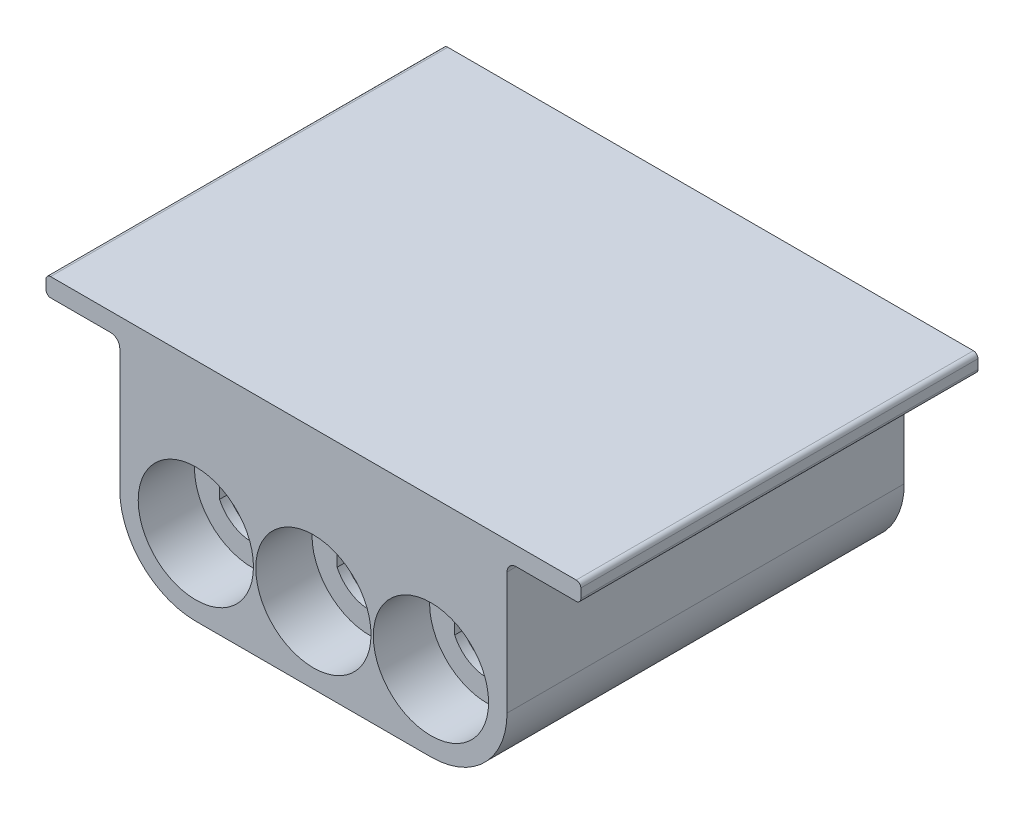
SolidWorks part; units mm, degrees
ref_plane "Front Plane" through (0, 0, 0) normal (0, 0, 1) x (1, 0, 0)
ref_plane "Top Plane" through (0, 0, 0) normal (0, 1, 0) x (1, 0, 0)
ref_plane "Right Plane" through (0, 0, 0) normal (1, 0, 0) x (0, 0, -1)
sketch "Sketch1" plane through (0, 0, 0) normal (0, 0, 1) x (1, 0, 0)
  line L0 (-163.5801, 21.2957) -> (-163.5801, 37.2957)
  line L5 (-147.0801, 53.7957) -> (-96.0801, 53.7957)
  line L6 (-79.5801, 21.2957) -> (-79.5801, 37.2957)
  line L7 (-147.0801, 4.7957) -> (-96.0801, 4.7957)
  circle A0 centre (-147.0801, 21.2957) radius 12.5
  circle A1 centre (-121.5801, 21.2957) radius 12.5
  circle A2 centre (-96.0801, 21.2957) radius 12.5
  arc A5 (-163.5801, 37.2957) -> (-147.0801, 53.7957) centre (-147.0801, 37.2957) cw
  arc A6 (-96.0801, 53.7957) -> (-79.5801, 37.2957) centre (-96.0801, 37.2957) cw
  arc A7 (-163.5801, 21.2957) -> (-147.0801, 4.7957) centre (-147.0801, 21.2957) ccw
  arc A8 (-96.0801, 4.7957) -> (-79.5801, 21.2957) centre (-96.0801, 21.2957) ccw
  circle A10 centre (-147.0801, 21.2957) radius 16.5 construction
  circle A11 centre (-96.0801, 21.2957) radius 16.5 construction
  point P9 (-96.0801, 8.7957)
  point P18 (-159.5801, 49.7957)
  point P20 (-147.0801, 8.7957)
  point P30 (-79.5801, 21.2957)
  point P35 (-130.5801, 21.2957)
  dimension "D1" = 25
  dimension "D2" = 25
  dimension "D3" = 25
  dimension "D6" = 84
  dimension "D4" = 16.5
  dimension "D5" = 4
  dimension "D7" = 49
extrude "Boss-Extrude1" add sketch "Sketch1" along normal blind 1.2
sketch "Sketch2" plane through (0, 0, 0) normal (0, 0, -1) x (-1, 0, 0)
  circle A0 centre (96.0801, 21.2957) radius 12.5 construction
  circle A1 centre (121.5801, 21.2957) radius 12.5 construction
  circle A2 centre (147.0801, 21.2957) radius 12.5 construction
  circle A3 centre (96.0801, 21.2957) radius 12.5
  circle A4 centre (121.5801, 21.2957) radius 12.5
  circle A5 centre (147.0801, 21.2957) radius 12.5
  arc A6 (135.2186, 15.1697) -> (135.2186, 27.4216) centre (147.0801, 21.2957) ccw
  arc A7 (109.7186, 15.1697) -> (133.4416, 15.1697) centre (121.5801, 21.2957) ccw
  arc A8 (107.9416, 27.4216) -> (107.9416, 15.1697) centre (96.0801, 21.2957) ccw
  arc A9 (133.4416, 27.4216) -> (109.7186, 27.4216) centre (121.5801, 21.2957) ccw
  circle A10 centre (121.5801, 21.2957) radius 13.35 construction
  circle A11 centre (96.0801, 21.2957) radius 13.35 construction
  arc A12 (107.9416, 27.4216) -> (109.7186, 27.4216) centre (108.8301, 27.8805) ccw
  circle A13 centre (147.0801, 21.2957) radius 13.35 construction
  arc A14 (109.7186, 15.1697) -> (107.9416, 15.1697) centre (108.8301, 14.7108) ccw
  arc A15 (133.4416, 27.4216) -> (135.2186, 27.4216) centre (134.3301, 27.8805) ccw
  arc A16 (133.4416, 15.1697) -> (135.2186, 15.1697) centre (134.3301, 14.7108) cw
  point P12 (109.4301, 21.2957)
  point P15 (134.9301, 21.2957)
  point P21 (160.4301, 21.2957)
  dimension "D2" = 1
  dimension "D1" = 0.85
extrude "Boss-Extrude2" add sketch "Sketch2" along normal blind 11
sketch "Sketch3" plane through (0, 0, -11) normal (0, 0, -1) x (-1, 0, 0)
  line L0 (89.3301, 18.1429) -> (89.3301, 24.4484)
  line L1 (89.3301, 18.1429) -> (89.3301, 24.4484)
  line L2 (102.8301, 18.1429) -> (102.8301, 24.4484)
  line L3 (102.8301, 18.1429) -> (102.8301, 24.4484)
  line L4 (128.3301, 18.1429) -> (128.3301, 24.4484)
  line L5 (128.3301, 18.1429) -> (128.3301, 24.4484)
  line L6 (114.8301, 18.1429) -> (114.8301, 24.4484)
  line L7 (114.8301, 18.1429) -> (114.8301, 24.4484)
  line L8 (140.3301, 24.4484) -> (140.3301, 18.1429)
  line L9 (140.3301, 24.4484) -> (140.3301, 18.1429)
  line L10 (153.8301, 24.4484) -> (153.8301, 18.1429)
  line L11 (153.8301, 24.4484) -> (153.8301, 18.1429)
  line L12 (128.6301, 18.077) -> (128.6301, 24.5144)
  line L13 (114.5301, 18.077) -> (114.5301, 24.5144)
  line L14 (103.1301, 18.077) -> (103.1301, 24.5144)
  line L15 (89.0301, 18.077) -> (89.0301, 24.5144)
  line L16 (154.1301, 24.5144) -> (154.1301, 18.077)
  line L17 (140.0301, 24.5144) -> (140.0301, 18.077)
  arc A0 (107.9416, 27.4216) -> (107.9416, 15.1697) centre (96.0801, 21.2957) ccw construction
  arc A1 (109.7186, 15.1697) -> (107.9416, 15.1697) centre (108.8301, 14.7108) ccw construction
  arc A2 (107.9416, 27.4216) -> (109.7186, 27.4216) centre (108.8301, 27.8805) ccw construction
  arc A3 (109.7186, 15.1697) -> (133.4416, 15.1697) centre (121.5801, 21.2957) ccw construction
  arc A4 (133.4416, 27.4216) -> (109.7186, 27.4216) centre (121.5801, 21.2957) ccw construction
  arc A5 (133.4416, 27.4216) -> (135.2186, 27.4216) centre (134.3301, 27.8805) ccw construction
  arc A6 (135.2186, 15.1697) -> (133.4416, 15.1697) centre (134.3301, 14.7108) ccw construction
  arc A7 (135.2186, 15.1697) -> (135.2186, 27.4216) centre (147.0801, 21.2957) ccw construction
  arc A8 (107.9416, 27.4216) -> (107.9416, 15.1697) centre (96.0801, 21.2957) ccw
  arc A9 (109.7186, 15.1697) -> (107.9416, 15.1697) centre (108.8301, 14.7108) ccw
  arc A10 (107.9416, 27.4216) -> (109.7186, 27.4216) centre (108.8301, 27.8805) ccw
  arc A11 (109.7186, 15.1697) -> (133.4416, 15.1697) centre (121.5801, 21.2957) ccw
  arc A12 (133.4416, 27.4216) -> (109.7186, 27.4216) centre (121.5801, 21.2957) ccw
  arc A13 (133.4416, 27.4216) -> (135.2186, 27.4216) centre (134.3301, 27.8805) ccw
  arc A14 (135.2186, 15.1697) -> (133.4416, 15.1697) centre (134.3301, 14.7108) ccw
  arc A15 (135.2186, 15.1697) -> (135.2186, 27.4216) centre (147.0801, 21.2957) ccw
  arc A16 (89.3301, 18.1429) -> (102.8301, 18.1429) centre (96.0801, 21.2957) ccw
  arc A17 (89.3301, 18.1429) -> (102.8301, 18.1429) centre (96.0801, 21.2957) ccw
  arc A18 (102.8301, 24.4484) -> (89.3301, 24.4484) centre (96.0801, 21.2957) ccw
  arc A19 (102.8301, 24.4484) -> (89.3301, 24.4484) centre (96.0801, 21.2957) ccw
  arc A20 (114.8301, 18.1429) -> (128.3301, 18.1429) centre (121.5801, 21.2957) ccw
  arc A21 (114.8301, 18.1429) -> (128.3301, 18.1429) centre (121.5801, 21.2957) ccw
  arc A22 (128.3301, 24.4484) -> (114.8301, 24.4484) centre (121.5801, 21.2957) ccw
  arc A23 (128.3301, 24.4484) -> (114.8301, 24.4484) centre (121.5801, 21.2957) ccw
  arc A24 (140.3301, 18.1429) -> (153.8301, 18.1429) centre (147.0801, 21.2957) ccw
  arc A25 (140.3301, 18.1429) -> (153.8301, 18.1429) centre (147.0801, 21.2957) ccw
  arc A26 (153.8301, 24.4484) -> (140.3301, 24.4484) centre (147.0801, 21.2957) ccw
  arc A27 (153.8301, 24.4484) -> (140.3301, 24.4484) centre (147.0801, 21.2957) ccw
  arc A28 (114.5301, 18.077) -> (128.6301, 18.077) centre (121.5801, 21.2957) ccw
  arc A29 (128.6301, 24.5144) -> (114.5301, 24.5144) centre (121.5801, 21.2957) ccw
  arc A30 (89.0301, 18.077) -> (103.1301, 18.077) centre (96.0801, 21.2957) ccw
  arc A31 (103.1301, 24.5144) -> (89.0301, 24.5144) centre (96.0801, 21.2957) ccw
  arc A32 (140.0301, 18.077) -> (154.1301, 18.077) centre (147.0801, 21.2957) ccw
  arc A33 (154.1301, 24.5144) -> (140.0301, 24.5144) centre (147.0801, 21.2957) ccw
  dimension "D1" = 0.3
extrude "Boss-Extrude3" add sketch "Sketch3" along normal blind 2 contours A33 L16 A32 L17 | A29 L12 A28 L13 | A31 L14 A30 L15 region at (-108.8301, 26.0589, -11)
sketch "Sketch4" plane through (0, 0, -13) normal (0, 0, -1) x (-1, 0, 0)
  line L0 (96.0801, 31.688) -> (87.0801, 26.4918) construction
  line L1 (87.0801, 26.4918) -> (87.0801, 16.0995) construction
  line L2 (87.0801, 16.0995) -> (96.0801, 10.9034) construction
  line L3 (96.0801, 10.9034) -> (105.0801, 16.0995) construction
  line L4 (105.0801, 16.0995) -> (105.0801, 26.4918) construction
  line L5 (105.0801, 26.4918) -> (96.0801, 31.688) construction
  line L6 (130.5801, 26.4918) -> (121.5801, 31.688) construction
  line L7 (121.5801, 31.688) -> (112.5801, 26.4918) construction
  line L8 (112.5801, 26.4918) -> (112.5801, 16.0995) construction
  line L9 (112.5801, 16.0995) -> (121.5801, 10.9034) construction
  line L10 (121.5801, 10.9034) -> (130.5801, 16.0995) construction
  line L11 (130.5801, 16.0995) -> (130.5801, 26.4918) construction
  line L12 (156.0801, 26.4918) -> (147.0801, 31.688) construction
  line L13 (147.0801, 31.688) -> (138.0801, 26.4918) construction
  line L14 (138.0801, 26.4918) -> (138.0801, 16.0995) construction
  line L15 (138.0801, 16.0995) -> (147.0801, 10.9034) construction
  line L16 (147.0801, 10.9034) -> (156.0801, 16.0995) construction
  line L17 (156.0801, 16.0995) -> (156.0801, 26.4918) construction
  line L18 (96.0801, 31.688) -> (87.0801, 26.4918)
  line L19 (87.0801, 26.4918) -> (87.0801, 16.0995)
  line L20 (87.0801, 16.0995) -> (96.0801, 10.9034)
  line L21 (96.0801, 10.9034) -> (105.0801, 16.0995)
  line L22 (105.0801, 16.0995) -> (105.0801, 26.4918)
  line L23 (105.0801, 26.4918) -> (96.0801, 31.688)
  line L24 (130.5801, 26.4918) -> (121.5801, 31.688)
  line L25 (121.5801, 31.688) -> (112.5801, 26.4918)
  line L26 (112.5801, 26.4918) -> (112.5801, 16.0995)
  line L27 (112.5801, 16.0995) -> (121.5801, 10.9034)
  line L28 (121.5801, 10.9034) -> (130.5801, 16.0995)
  line L29 (130.5801, 16.0995) -> (130.5801, 26.4918)
  line L30 (156.0801, 26.4918) -> (147.0801, 31.688)
  line L31 (147.0801, 31.688) -> (138.0801, 26.4918)
  line L32 (138.0801, 26.4918) -> (138.0801, 16.0995)
  line L33 (138.0801, 16.0995) -> (147.0801, 10.9034)
  line L34 (147.0801, 10.9034) -> (156.0801, 16.0995)
  line L35 (156.0801, 16.0995) -> (156.0801, 26.4918)
  line L36 (147.0801, 10.5569) -> (156.3801, 15.9263)
  line L37 (156.3801, 15.9263) -> (156.3801, 26.665)
  line L38 (156.3801, 26.665) -> (147.0801, 32.0344)
  line L39 (147.0801, 32.0344) -> (137.7801, 26.665)
  line L40 (137.7801, 26.665) -> (137.7801, 15.9263)
  line L41 (137.7801, 15.9263) -> (147.0801, 10.5569)
  line L42 (121.5801, 10.5569) -> (130.8801, 15.9263)
  line L43 (130.8801, 15.9263) -> (130.8801, 26.665)
  line L44 (130.8801, 26.665) -> (121.5801, 32.0344)
  line L45 (121.5801, 32.0344) -> (112.2801, 26.665)
  line L46 (112.2801, 26.665) -> (112.2801, 15.9263)
  line L47 (112.2801, 15.9263) -> (121.5801, 10.5569)
  line L48 (96.0801, 10.5569) -> (105.3801, 15.9263)
  line L49 (105.3801, 15.9263) -> (105.3801, 26.665)
  line L50 (105.3801, 26.665) -> (96.0801, 32.0344)
  line L51 (96.0801, 32.0344) -> (86.7801, 26.665)
  line L52 (86.7801, 26.665) -> (86.7801, 15.9263)
  line L53 (86.7801, 15.9263) -> (96.0801, 10.5569)
  circle A0 centre (147.0801, 21.2957) radius 12
  circle A1 centre (121.5801, 21.2957) radius 12
  circle A2 centre (96.0801, 21.2957) radius 12
  dimension "D1" = 0.3
extrude "Boss-Extrude4" add sketch "Sketch4" along normal up to surface (5.3 mm away) contours A2 L53 L52 L51 L50 L49 L48 | A1 L47 L46 L45 L44 L43 L42 | A0 L41 L40 L39 L38 L37 L36 region at (-135.4195, 21.2957, -13) region at (-109.9195, 21.2957, -13) region at (-84.4195, 21.2957, -13)
sketch "Sketch5" plane through (0, 0, 0) normal (0, 0, -1) x (-1, 0, 0)
  line L0 (79.5801, 21.2957) -> (79.5801, 37.2957) construction
  line L1 (96.0801, 53.7957) -> (147.0801, 53.7957) construction
  line L2 (163.5801, 37.2957) -> (163.5801, 21.2957) construction
  line L3 (147.0801, 4.7957) -> (96.0801, 4.7957) construction
  line L4 (79.5801, 21.2957) -> (79.5801, 37.2957)
  line L5 (96.0801, 53.7957) -> (147.0801, 53.7957)
  line L6 (163.5801, 37.2957) -> (163.5801, 21.2957)
  line L7 (147.0801, 4.7957) -> (96.0801, 4.7957)
  line L8 (160.2801, 37.2957) -> (160.2801, 21.2957)
  line L9 (96.0801, 50.4957) -> (147.0801, 50.4957)
  line L10 (82.8801, 21.2957) -> (82.8801, 37.2957)
  line L11 (147.0801, 8.0957) -> (96.0801, 8.0957)
  arc A0 (79.5801, 21.2957) -> (96.0801, 4.7957) centre (96.0801, 21.2957) ccw construction
  arc A1 (96.0801, 53.7957) -> (79.5801, 37.2957) centre (96.0801, 37.2957) ccw construction
  arc A2 (163.5801, 37.2957) -> (147.0801, 53.7957) centre (147.0801, 37.2957) ccw construction
  arc A3 (147.0801, 4.7957) -> (163.5801, 21.2957) centre (147.0801, 21.2957) ccw construction
  arc A4 (79.5801, 21.2957) -> (96.0801, 4.7957) centre (96.0801, 21.2957) ccw
  arc A5 (96.0801, 53.7957) -> (79.5801, 37.2957) centre (96.0801, 37.2957) ccw
  arc A6 (163.5801, 37.2957) -> (147.0801, 53.7957) centre (147.0801, 37.2957) ccw
  arc A7 (147.0801, 4.7957) -> (163.5801, 21.2957) centre (147.0801, 21.2957) ccw
  arc A8 (147.0801, 8.0957) -> (160.2801, 21.2957) centre (147.0801, 21.2957) ccw
  arc A9 (160.2801, 37.2957) -> (147.0801, 50.4957) centre (147.0801, 37.2957) ccw
  arc A10 (96.0801, 50.4957) -> (82.8801, 37.2957) centre (96.0801, 37.2957) ccw
  arc A11 (82.8801, 21.2957) -> (96.0801, 8.0957) centre (96.0801, 21.2957) ccw
  dimension "D1" = 3.3
extrude "Boss-Extrude5" add sketch "Sketch5" along normal up to surface (84.455 mm away)
sketch "Sketch6" plane through (0, 0, -84.455) normal (0, 0, -1) x (-1, 0, 0)
  line L0 (147.0801, 4.7957) -> (96.0801, 4.7957) construction
  line L1 (163.5801, 37.2957) -> (163.5801, 21.2957) construction
  line L2 (96.0801, 53.7957) -> (147.0801, 53.7957) construction
  line L3 (79.5801, 21.2957) -> (79.5801, 37.2957) construction
  line L4 (82.8801, 21.2957) -> (82.8801, 37.2957) construction
  line L5 (96.0801, 50.4957) -> (147.0801, 50.4957) construction
  line L6 (160.2801, 37.2957) -> (160.2801, 21.2957) construction
  line L7 (147.0801, 8.0957) -> (96.0801, 8.0957) construction
  line L8 (147.0801, 4.7957) -> (96.0801, 4.7957)
  line L9 (163.5801, 37.2957) -> (163.5801, 21.2957)
  line L10 (96.0801, 53.7957) -> (147.0801, 53.7957)
  line L11 (79.5801, 21.2957) -> (79.5801, 37.2957)
  line L12 (82.8801, 21.2957) -> (82.8801, 37.2957)
  line L13 (96.0801, 50.4957) -> (147.0801, 50.4957)
  line L14 (160.2801, 37.2957) -> (160.2801, 21.2957)
  line L15 (147.0801, 8.0957) -> (96.0801, 8.0957)
  arc A0 (147.0801, 4.7957) -> (163.5801, 21.2957) centre (147.0801, 21.2957) ccw construction
  arc A1 (163.5801, 37.2957) -> (147.0801, 53.7957) centre (147.0801, 37.2957) ccw construction
  arc A2 (96.0801, 53.7957) -> (79.5801, 37.2957) centre (96.0801, 37.2957) ccw construction
  arc A3 (79.5801, 21.2957) -> (96.0801, 4.7957) centre (96.0801, 21.2957) ccw construction
  arc A4 (82.8801, 21.2957) -> (96.0801, 8.0957) centre (96.0801, 21.2957) ccw construction
  arc A5 (96.0801, 50.4957) -> (82.8801, 37.2957) centre (96.0801, 37.2957) ccw construction
  arc A6 (160.2801, 37.2957) -> (147.0801, 50.4957) centre (147.0801, 37.2957) ccw construction
  arc A7 (147.0801, 8.0957) -> (160.2801, 21.2957) centre (147.0801, 21.2957) ccw construction
  arc A8 (147.0801, 4.7957) -> (163.5801, 21.2957) centre (147.0801, 21.2957) ccw
  arc A9 (163.5801, 37.2957) -> (147.0801, 53.7957) centre (147.0801, 37.2957) ccw
  arc A10 (96.0801, 53.7957) -> (79.5801, 37.2957) centre (96.0801, 37.2957) ccw
  arc A11 (79.5801, 21.2957) -> (96.0801, 4.7957) centre (96.0801, 21.2957) ccw
  arc A12 (82.8801, 21.2957) -> (96.0801, 8.0957) centre (96.0801, 21.2957) ccw
  arc A13 (96.0801, 50.4957) -> (82.8801, 37.2957) centre (96.0801, 37.2957) ccw
  arc A14 (160.2801, 37.2957) -> (147.0801, 50.4957) centre (147.0801, 37.2957) ccw
  arc A15 (147.0801, 8.0957) -> (160.2801, 21.2957) centre (147.0801, 21.2957) ccw
extrude "Boss-Extrude6" add sketch "Sketch6" along normal blind 0.5
sketch "Sketch7" plane through (0, 0, 0) normal (0, 0, -1) x (-1, 0, 0)
  line L4 (150.4651, 40.188) -> (147.9651, 40.188)
  line L5 (150.4651, 40.188) -> (92.6801, 40.188) construction
  line L6 (147.9651, 39.988) -> (147.9651, 38.188)
  line L7 (147.9651, 38.188) -> (160.2499, 38.188)
  line L8 (147.9651, 41.988) -> (147.9651, 43.788)
  line L10 (147.9651, 43.788) -> (158.5731, 43.788)
  line L12 (147.9651, 39.988) -> (150.6651, 39.988)
  line L13 (150.6651, 41.988) -> (150.6651, 39.988)
  line L14 (147.9651, 41.988) -> (150.6651, 41.988)
  line L16 (95.1801, 39.988) -> (95.1801, 38.188)
  line L17 (95.1801, 38.188) -> (82.9103, 38.188)
  line L20 (95.1801, 41.988) -> (95.1801, 43.788)
  line L21 (95.1801, 43.788) -> (84.587, 43.788)
  line L22 (92.4801, 41.988) -> (95.1801, 41.988)
  line L23 (92.4801, 39.988) -> (92.4801, 41.988)
  line L24 (92.4801, 39.988) -> (95.1801, 39.988)
  arc A0 (96.0801, 50.4957) -> (82.8801, 37.2957) centre (96.0801, 37.2957) ccw construction
  arc A1 (160.2801, 37.2957) -> (147.0801, 50.4957) centre (147.0801, 37.2957) ccw construction
  arc A2 (84.587, 43.788) -> (82.9103, 38.188) centre (96.0801, 37.2957) ccw
  arc A3 (160.2499, 38.188) -> (158.5731, 43.788) centre (147.0801, 37.2957) ccw
  arc M5 (160.2801, 37.2957) -> (147.0801, 50.4957) centre (147.0801, 37.2957) ccw
  arc M7 (96.0801, 50.4957) -> (82.8801, 37.2957) centre (96.0801, 37.2957) ccw
extrude "Boss-Extrude7" add sketch "Sketch7" along normal blind 84 contours L8 L14 L13 L12 L6 L7 L10 M5 | L24 L23 L22 L20 L21 L17 L16 M7 region at (-154.2178, 40.9157, 0) region at (-88.935, 40.9156, 0)
fillet "Fillet1" radius 1 4 edges at (-84.587, 43.788, -42) (-82.9103, 38.188, -42) (-158.5731, 43.788, -42) (-160.2499, 38.188, -42) tangent propagation no
fillet "Fillet2" radius 1 8 edges at (-95.1801, 43.788, -42) (-95.1801, 41.988, -42) (-95.1801, 39.988, -42) (-95.1801, 38.188, -42) (-147.9651, 43.788, -42) (-147.9651, 41.988, -42) (-147.9651, 39.988, -42) (-147.9651, 38.188, -42)
ref_plane "Plane1" through (0, 0, -79.955) normal (0, 0, -1) x (-1, 0, 0)
ref_plane "Plane2" through (0, 29.2957, 0) normal (0, -1, 0) x (-1, 0, 0)
sketch "Sketch10" plane through (0, 0, -84.955) normal (0, 0, -1) x (-1, 0, 0)
  line L0 (160.2801, 21.2957) -> (160.2801, 37.2957) construction
  line L1 (163.5801, 21.2957) -> (163.5801, 37.2957) construction
  line L2 (96.0801, 4.7957) -> (147.0801, 4.7957) construction
  line L3 (96.0801, 8.0957) -> (147.0801, 8.0957) construction
  line L4 (79.5801, 37.2957) -> (79.5801, 21.2957) construction
  line L5 (82.8801, 37.2957) -> (82.8801, 21.2957) construction
  line L6 (147.0801, 53.7957) -> (96.0801, 53.7957) construction
  line L7 (147.0801, 50.4957) -> (96.0801, 50.4957) construction
  line L8 (160.2801, 21.2957) -> (160.2801, 37.2957)
  line L9 (163.5801, 21.2957) -> (163.5801, 37.2957)
  line L10 (96.0801, 4.7957) -> (147.0801, 4.7957)
  line L11 (96.0801, 8.0957) -> (147.0801, 8.0957)
  line L12 (79.5801, 37.2957) -> (79.5801, 21.2957)
  line L13 (82.8801, 37.2957) -> (82.8801, 21.2957)
  line L14 (147.0801, 53.7957) -> (96.0801, 53.7957)
  line L15 (147.0801, 50.4957) -> (96.0801, 50.4957)
  line L16 (82.8801, 21.2957) -> (96.0801, 8.0957)
  line L17 (160.2801, 21.2957) -> (147.0801, 8.0957)
  arc A0 (163.5801, 37.2957) -> (147.0801, 53.7957) centre (147.0801, 37.2957) ccw construction
  arc A1 (160.2801, 37.2957) -> (147.0801, 50.4957) centre (147.0801, 37.2957) ccw construction
  arc A2 (147.0801, 8.0957) -> (160.2801, 21.2957) centre (147.0801, 21.2957) ccw construction
  arc A3 (147.0801, 4.7957) -> (163.5801, 21.2957) centre (147.0801, 21.2957) ccw construction
  arc A4 (79.5801, 21.2957) -> (96.0801, 4.7957) centre (96.0801, 21.2957) ccw construction
  arc A5 (82.8801, 21.2957) -> (96.0801, 8.0957) centre (96.0801, 21.2957) ccw construction
  arc A6 (96.0801, 53.7957) -> (79.5801, 37.2957) centre (96.0801, 37.2957) ccw construction
  arc A7 (96.0801, 50.4957) -> (82.8801, 37.2957) centre (96.0801, 37.2957) ccw construction
  arc A8 (163.5801, 37.2957) -> (147.0801, 53.7957) centre (147.0801, 37.2957) ccw
  arc A9 (160.2801, 37.2957) -> (147.0801, 50.4957) centre (147.0801, 37.2957) ccw
  arc A10 (147.0801, 8.0957) -> (160.2801, 21.2957) centre (147.0801, 21.2957) ccw
  arc A11 (147.0801, 4.7957) -> (163.5801, 21.2957) centre (147.0801, 21.2957) ccw
  arc A12 (79.5801, 21.2957) -> (96.0801, 4.7957) centre (96.0801, 21.2957) ccw
  arc A13 (82.8801, 21.2957) -> (96.0801, 8.0957) centre (96.0801, 21.2957) ccw
  arc A14 (96.0801, 53.7957) -> (79.5801, 37.2957) centre (96.0801, 37.2957) ccw
  arc A15 (96.0801, 50.4957) -> (82.8801, 37.2957) centre (96.0801, 37.2957) ccw
  arc M10 (96.0801, 8.0957) -> (82.8801, 21.2957) centre (96.0801, 21.2957) cw
  arc M16 (160.2801, 21.2957) -> (147.0801, 8.0957) centre (147.0801, 21.2957) cw
extrude "Boss-Extrude8" add sketch "Sketch10" against normal blind 10 contours L16 M10 | L17 M16 region at (-154.7886, 13.5871, -84.955) region at (-88.3716, 13.5871, -84.955)
chamfer "Chamfer2" distance 4 angle 45 2 edges at (-153.6801, 14.6957, -74.955) (-89.4801, 14.6957, -74.955)
sketch "Sketch11" plane through (0, 0, -84.955) normal (0, 0, -1) x (-1, 0, 0)
  line L0 (82.8801, 21.2957) -> (96.0801, 8.0957) construction
  line L1 (160.2801, 21.2957) -> (147.0801, 8.0957) construction
  line L2 (148.9651, 38.188) -> (159.2801, 38.188) construction
  line L3 (148.9651, 43.788) -> (156.7084, 43.788) construction
  line L4 (94.1801, 38.188) -> (83.8801, 38.188) construction
  line L5 (94.1801, 43.788) -> (86.4517, 43.788) construction
  line L6 (82.8801, 21.2957) -> (96.0801, 8.0957)
  line L7 (160.2801, 21.2957) -> (147.0801, 8.0957)
  line L8 (148.9651, 38.188) -> (159.2801, 38.188)
  line L9 (148.9651, 43.788) -> (156.7084, 43.788)
  line L10 (94.1801, 38.188) -> (83.8801, 38.188)
  line L11 (94.1801, 43.788) -> (86.4517, 43.788)
  line L12 (89.0301, 38.188) -> (89.0301, 43.788) construction
  line L13 (154.1226, 38.188) -> (154.1226, 43.788) construction
  line L14 (153.6801, 14.6957) -> (158.7473, 9.6284) construction
  line L15 (89.4801, 14.6957) -> (84.4128, 9.6284) construction
  arc A0 (79.5801, 21.2957) -> (96.0801, 4.7957) centre (96.0801, 21.2957) ccw construction
  arc A1 (147.0801, 4.7957) -> (163.5801, 21.2957) centre (147.0801, 21.2957) ccw construction
  arc A2 (79.5801, 21.2957) -> (96.0801, 4.7957) centre (96.0801, 21.2957) ccw
  arc A3 (147.0801, 4.7957) -> (163.5801, 21.2957) centre (147.0801, 21.2957) ccw
  circle A4 centre (86.9465, 12.162) radius 1.25
  circle A5 centre (156.2137, 12.162) radius 1.25
  circle A6 centre (89.0301, 40.988) radius 1.25
  circle A7 centre (154.1226, 40.988) radius 1.25
extrude "Cut-Extrude1" cut sketch "Sketch11" against normal blind 20 contours A6 | A4 | A5 | A7 region at (-86.9465, 12.162, -84.955) region at (-156.2137, 12.162, -84.955) region at (-89.0301, 40.988, -84.955) region at (-154.1226, 40.988, -84.955)
sketch "Sketch13" plane through (0, 0, 1.2) normal (0, 0, 1) x (1, 0, 0)
  line L0 (-96.0801, 53.7957) -> (-72.0801, 53.7957)
  line L1 (-79.5801, 37.2957) -> (-79.5801, 47.7957)
  line L2 (-163.5801, 37.2957) -> (-163.5801, 47.7957)
  line L3 (-77.5801, 49.7957) -> (-64.5801, 49.7957)
  line L4 (-165.5801, 49.7957) -> (-178.5801, 49.7957)
  line L5 (-179.5801, 50.7957) -> (-179.5801, 52.7957)
  line L6 (-178.5801, 53.7957) -> (-147.0801, 53.7957)
  line L8 (-63.5801, 50.7957) -> (-63.5801, 52.7957)
  line L9 (-64.5801, 53.7957) -> (-72.0801, 53.7957)
  arc A0 (-147.0801, 53.7957) -> (-163.5801, 37.2957) centre (-147.0801, 37.2957) ccw construction
  arc A1 (-79.5801, 37.2957) -> (-96.0801, 53.7957) centre (-96.0801, 37.2957) ccw construction
  arc A2 (-147.0801, 53.7957) -> (-163.5801, 37.2957) centre (-147.0801, 37.2957) ccw
  arc A3 (-79.5801, 37.2957) -> (-96.0801, 53.7957) centre (-96.0801, 37.2957) ccw
  arc A4 (-179.5801, 52.7957) -> (-178.5801, 53.7957) centre (-178.5801, 52.7957) cw
  arc A5 (-178.5801, 49.7957) -> (-179.5801, 50.7957) centre (-178.5801, 50.7957) cw
  arc A6 (-63.5801, 52.7957) -> (-64.5801, 53.7957) centre (-64.5801, 52.7957) ccw
  arc A7 (-64.5801, 49.7957) -> (-63.5801, 50.7957) centre (-64.5801, 50.7957) ccw
  arc A8 (-163.5801, 47.7957) -> (-165.5801, 49.7957) centre (-165.5801, 47.7957) ccw
  arc A9 (-79.5801, 47.7957) -> (-77.5801, 49.7957) centre (-77.5801, 47.7957) cw
  dimension "D1" = 1
  dimension "D2" = 2
extrude "Boss-Extrude10" add sketch "Sketch13" against normal up to surface (86.155 mm away) contours A2 L2 A8 L4 A5 L5 A4 L6 | L0 L9 A6 L8 A7 L3 A9 L1 A3 up to face at (-88.1965, 12.162, -84.955)
